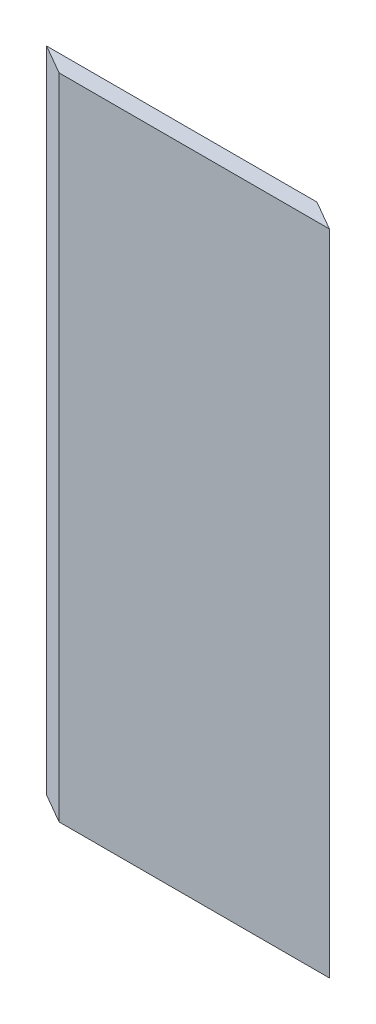
SolidWorks part; units mm, degrees
ref_plane "Front Plane" through (0, 0, 0) normal (0, 0, 1) x (1, 0, 0)
ref_plane "Top Plane" through (0, 0, 0) normal (0, 1, 0) x (1, 0, 0)
ref_plane "Right Plane" through (0, 0, 0) normal (1, 0, 0) x (0, 0, -1)
sketch "Sketch1" plane through (0, 0, 0) normal (0, 0, 1) x (1, 0, 0)
  line L0 (53.7926, 0) -> (53.7926, -121.92)
  line L1 (53.7926, -121.92) -> (2.9926, -121.92)
  line L2 (2.9926, -121.92) -> (2.9926, 0)
  line L3 (2.9926, 0) -> (53.7926, 0)
extrude "Boss-Extrude1" add sketch "Sketch1" against normal blind 3.2
sketch "Sketch2" plane through (0, -121.92, 0) normal (0, -1, 0) x (1, 0, 0)
  line L0 (53.7926, 0) -> (53.7926, -3.2)
  line L1 (53.7926, -3.2) -> (48.2501, -3.2)
  line L2 (2.9926, -3.2) -> (53.7926, -3.2) construction
  line L3 (-56.1926, -63.5) -> (53.7926, 0) construction
  line L4 (48.2501, -3.2) -> (53.7926, 0)
extrude "Cut-Extrude1" cut sketch "Sketch2" against normal through all
sketch "Sketch4" plane through (0, -121.92, 0) normal (0, -1, 0) x (1, 0, 0)
  line L0 (2.9926, 0) -> (2.9926, -3.2)
  line L1 (2.9926, -3.2) -> (-2.5499, -3.2)
  line L3 (-2.5499, -3.2) -> (2.9926, 0)
  point P4 (0, 0)
extrude "Boss-Extrude2" add sketch "Sketch4" against normal up to surface (121.92 mm away) up to face at (27.007, 0, -1.6)
